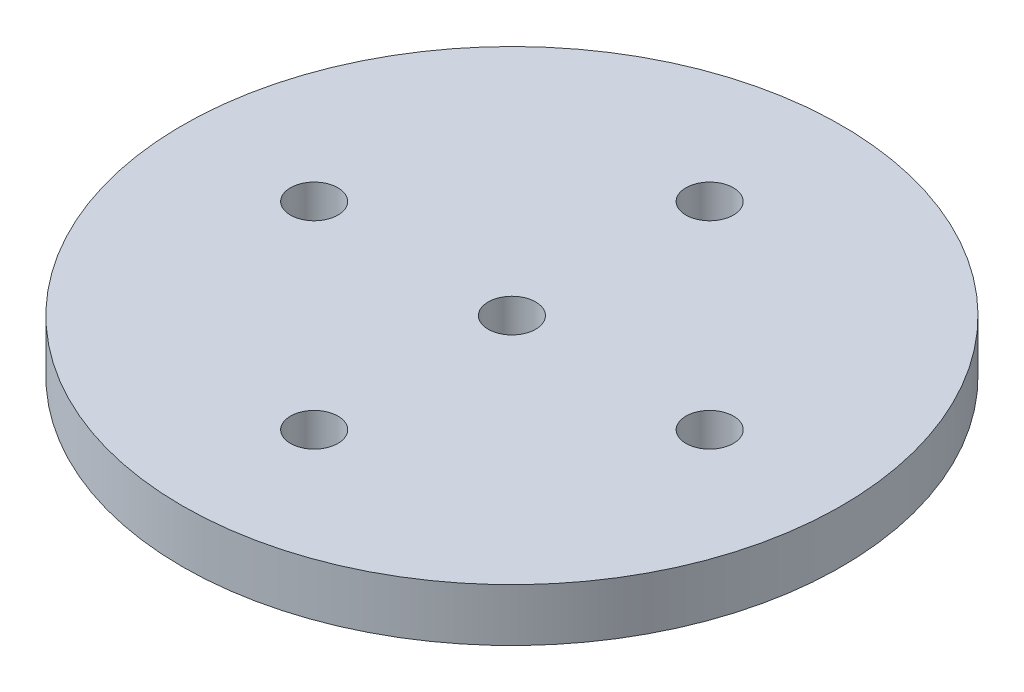
SolidWorks part; units mm, degrees
ref_plane "Alzado" through (0, 0, 0) normal (0, 0, 1) x (1, 0, 0)
ref_plane "Planta" through (0, 0, 0) normal (0, 1, 0) x (1, 0, 0)
ref_plane "Vista lateral" through (0, 0, 0) normal (1, 0, 0) x (0, 0, -1)
sketch "Croquis1" plane through (0, 0, 0) normal (0, 1, 0) x (1, 0, 0)
  circle A0 centre (0, 0) radius 12.5
  circle A1 centre (0, 0) radius 4.5
  circle A2 centre (0, 0) radius 2.9
  dimension "D1" = 25
  dimension "D2" = 5.8
  dimension "D3" = 9
extrude "Saliente-Extruir1" add sketch "Croquis1" along normal blind 2 contours A1 A2 | A2 | A0 A1 region at (-12.1464, 0, 0) region at (-4.3727, 0, 0) region at (0, 0, 0)
extrude "Saliente-Extruir2" add sketch "Croquis1<3>" against normal blind 4 contours A1 | A2
sketch "Croquis1<3>" plane through (0, 0, 0) normal (0, 1, 0) x (1, 0, 0) same geometry as "Croquis1"
sketch "Croquis2" plane through (0, 2, 0) normal (0, 1, 0) x (1, 0, 0)
  circle A0 centre (0, 0) radius 0.8
  circle A1 centre (7.5, 0) radius 0.8
  circle A2 centre (0, -7.5) radius 0.8
  circle A3 centre (-7.5, 0) radius 0.8
  circle A4 centre (0, 7.5) radius 0.8
  point P14 (0, 0)
  dimension "D1" = 1.6
  dimension "D2" = 7.5
  dimension "D3" = 4
hole_wizard "Taladro de margen para M1.61" positions "Croquis3D2" profile "Croquis5" hole size "M1.6" standard "Ansi Metric" end condition up to next
sketch3d "Croquis3D2"
  point P0 (0, 2, 0)
  point P3 (0, 2, -7.5)
  point P6 (7.5, 2, 0)
  point P9 (0, 2, 7.5)
  point P12 (-7.5, 2, 0)
sketch "Croquis5" plane through (0, 2, 0) normal (1, 0, 0) x (0, 0, 1)
  line L0 (0, 0) -> (0, 2)
  line L1 (0, 2) -> (0.9, 2)
  line L2 (0.9, 2) -> (0.9, 0)
  line L5 (0.9, 0) -> (0, 0)
  line L11 (0, -6.35) -> (0, 107.95) construction
  dimension "Diámetro de taladro hasta el siguiente" = 1.8
  dimension "Profundidad de taladro hasta el siguiente" = 2
